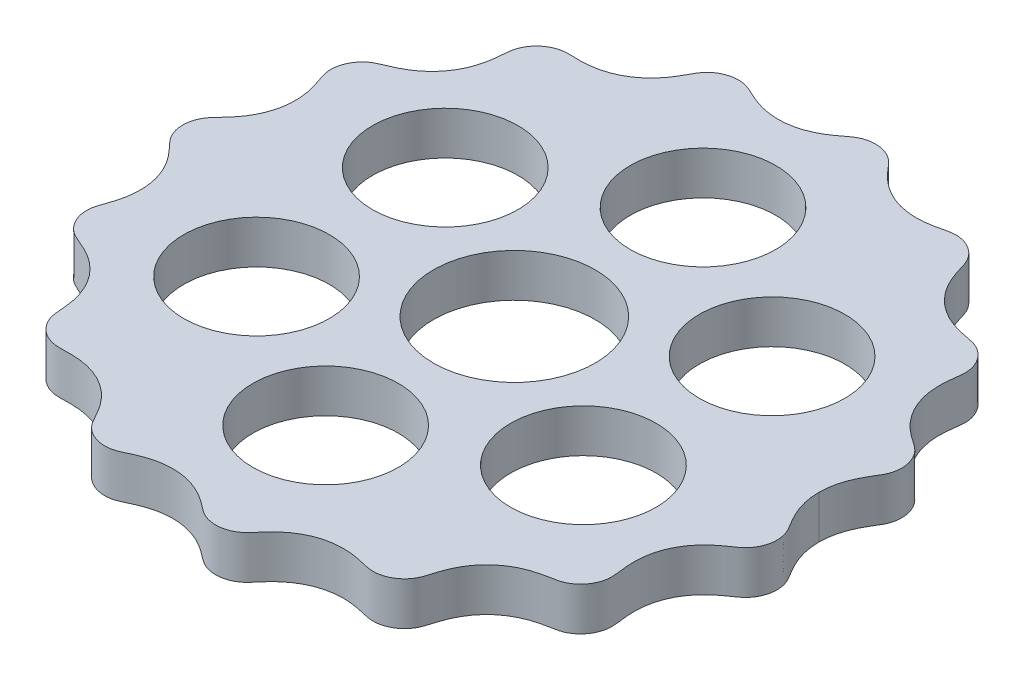
SolidWorks part; units mm, degrees
ref_plane "Front Plane" through (0, 0, 0) normal (0, 0, 1) x (1, 0, 0)
ref_plane "Top Plane" through (0, 0, 0) normal (0, 1, 0) x (1, 0, 0)
ref_plane "Right Plane" through (0, 0, 0) normal (1, 0, 0) x (0, 0, -1)
sketch "Sketch2" plane through (0, 0, 0) normal (0, 1, 0) x (1, 0, 0)
  circle A0 centre (0, 0) radius 35
  circle A1 centre (0, 35) radius 5.5
  circle A2 centre (13.3939, 32.3358) radius 5.5
  circle A3 centre (24.7487, 24.7487) radius 5.5
  circle A4 centre (32.3358, 13.3939) radius 5.5
  circle A5 centre (35, 0) radius 5.5
  circle A6 centre (32.3358, -13.3939) radius 5.5
  circle A7 centre (24.7487, -24.7487) radius 5.5
  circle A8 centre (13.3939, -32.3358) radius 5.5
  circle A9 centre (0, -35) radius 5.5
  circle A10 centre (-13.3939, -32.3358) radius 5.5
  circle A11 centre (-24.7487, -24.7487) radius 5.5
  circle A12 centre (-32.3358, -13.3939) radius 5.5
  circle A13 centre (-35, 0) radius 5.5
  circle A14 centre (-32.3358, 13.3939) radius 5.5
  circle A15 centre (-24.7487, 24.7487) radius 5.5
  circle A16 centre (-13.3939, 32.3358) radius 5.5
  point P14 (0, 0)
  dimension "D1" = 70
  dimension "D2" = 11
  dimension "D3" = 16
sketch "Sketch3" plane through (0, 0, 0) normal (0, 1, 0) x (1, 0, 0)
  line L0 (0, 0) -> (1.25, 0)
  circle A0 centre (1.25, 0) radius 17.5
  circle A1 centre (1.25, 0) radius 7.5
  circle A2 centre (1.25, 17.5) radius 6.75
  circle A3 centre (16.4054, 8.75) radius 6.75
  circle A4 centre (16.4054, -8.75) radius 6.75
  circle A5 centre (1.25, -17.5) radius 6.75
  circle A6 centre (-13.9054, -8.75) radius 6.75
  circle A7 centre (-13.9054, 8.75) radius 6.75
  spline S0 degree 4 poles (31.1366, 6.9847) (31.203, 6.8351) (31.3134, 6.5262) (31.4099, 6.0483) (31.4002, 5.404) (31.2697, 4.8647) (31.0757, 4.4461) (30.8859, 4.1207) (30.7324, 3.8696) (30.5414, 3.5556) (30.3222, 3.1725) (30.1219, 2.7738) (29.947, 2.3583) (29.8196, 1.9985) (29.7291, 1.6992) (29.6529, 1.3958) (29.5916, 1.0892) (29.551, 0.8187) (29.5259, 0.5847) (29.5113, 0.3932) (29.5036, 0.2322) (29.4998, 0.0635) (29.4996, -0.048) (29.5028, -0.2) (29.5088, -0.3457) (29.52, -0.516) (29.5395, -0.7199) (29.5727, -0.9729) (29.6257, -1.2689) (29.6959, -1.5759) (29.7851, -1.8912) (29.9157, -2.2793) (30.102, -2.7349) (30.335, -3.2008) (30.6126, -3.6776) (30.9341, -4.194) (31.2372, -4.7273) (31.4061, -5.3785) (31.4057, -6.1172) (31.2483, -6.8003) (30.9464, -7.4095) (30.5187, -7.9124) (30.0245, -8.2774) (29.5502, -8.595) (29.0554, -8.9568) (28.5566, -9.3788) (28.0713, -9.8763) (27.6188, -10.4563) (27.2335, -11.0884) (26.9232, -11.7651) (26.6937, -12.4782) (26.5492, -13.2173) (26.4929, -13.9285) (26.5065, -14.6008) (26.5673, -15.2309) (26.6512, -15.8162) (26.7167, -16.4473) (26.6264, -17.121) (26.3588, -17.7823) (25.9182, -18.3869) (25.3813, -18.8362) (24.7951, -19.1235) (24.2042, -19.2597) (23.6514, -19.3544) (23.1491, -19.4609) (22.7015, -19.5807) (22.2213, -19.7396) (21.7138, -19.9467) (21.1456, -20.242) (20.5337, -20.6545) (19.9693, -21.14) (19.4622, -21.6938) (19.0208, -22.3087) (18.6716, -22.937) (18.4029, -23.561) (18.1966, -24.1685) (18.0312, -24.7466) (17.8368, -25.3596) (17.4818, -25.9474) (16.963, -26.4532) (16.3026, -26.8344) (15.6052, -27.0309) (14.9186, -27.0444) (14.2906, -26.9063) (13.7073, -26.7605) (13.0779, -26.6354) (12.4032, -26.5561) (11.6845, -26.5443) (10.9313, -26.6191) (10.1981, -26.7814) (9.4956, -27.0274) (8.9144, -27.311) (8.4468, -27.5971) (8.0759, -27.8635) (7.7913, -28.0922) (7.4816, -28.3679) (7.1541, -28.6957) (6.8107, -29.0774) (6.4523, -29.5087) (6.0389, -29.9524) (5.497, -30.3164) (4.8394, -30.5567) (4.0956, -30.636) (3.389, -30.5371) (2.7605, -30.2784) (2.2467, -29.9061) (1.7817, -29.5409) (1.2664, -29.1732) (0.691, -28.8252) (0.0469, -28.5184) (-0.6654, -28.274) (-1.3977, -28.1162) (-2.139, -28.0466) (-2.879, -28.0642) (-3.6075, -28.1661) (-4.2811, -28.3376) (-4.8959, -28.5586) (-5.4566, -28.8062) (-5.9687, -29.0581) (-6.5321, -29.3036) (-7.1813, -29.4226) (-7.8826, -29.3781) (-8.5943, -29.1523) (-9.1983, -28.7803) (-9.6679, -28.2978) (-9.9878, -27.7564) (-10.2605, -27.2379) (-10.5768, -26.6962) (-10.9537, -26.1469) (-11.4088, -25.606) (-11.9502, -25.0925) (-12.5482, -24.6454) (-13.1945, -24.2723) (-13.8806, -23.9779) (-14.596, -23.7658) (-15.292, -23.6421) (-15.9562, -23.5904) (-16.5834, -23.5873) (-17.1688, -23.6104) (-17.7977, -23.6041) (-18.4504, -23.4386) (-19.0745, -23.1016) (-19.6258, -22.5981) (-20.0151, -22.013) (-20.2366, -21.3913) (-20.3057, -20.7807) (-20.3436, -20.2113) (-20.4095, -19.6018) (-20.5256, -18.9589) (-20.7138, -18.2898) (-20.9898, -17.608) (-21.3446, -16.9582) (-21.7755, -16.3511) (-22.2783, -15.7958) (-22.8461, -15.3011) (-23.4339, -14.8967) (-24.0229, -14.5724) (-24.599, -14.31) (-25.1478, -14.0899) (-25.7271, -13.8311) (-26.2654, -13.4161) (-26.7043, -12.8537) (-27.0076, -12.1698) (-27.1282, -11.4802) (-27.084, -10.8288) (-26.9064, -10.2491) (-26.7122, -9.7229) (-26.5247, -9.1481) (-26.3661, -8.5215) (-26.2605, -7.84) (-26.2278, -7.1092) (-26.2792, -6.3728) (-26.4175, -5.6414) (-26.6435, -4.9254) (-26.9163, -4.3218) (-27.1985, -3.8299) (-27.4942, -3.3917) (-27.7933, -3.0033) (-28.1536, -2.592) (-28.5722, -2.1595) (-28.9092, -1.79) (-29.1246, -1.4556) (-29.2527, -1.1931) (-29.3238, -1.0179) (-29.3829, -0.8388) (-29.4302, -0.6555) (-29.4612, -0.4933) (-29.4803, -0.3554) (-29.4914, -0.2338) (-29.4973, -0.1324) (-29.5007, -0.0226) (-29.5, 0.059) (-29.4956, 0.1702) (-29.4865, 0.2945) (-29.4732, 0.4119) (-29.4519, 0.545) (-29.4193, 0.6991) (-29.3684, 0.8884) (-29.2999, 1.0847) (-29.211, 1.2861) (-29.099, 1.4891) (-28.9873, 1.6605) (-28.8641, 1.8237) (-28.732, 1.9798) (-28.56, 2.1688) (-28.311, 2.4302) (-27.9922, 2.7711) (-27.6241, 3.2099) (-27.2613, 3.7219) (-26.8678, 4.4005) (-26.5022, 5.2703) (-26.3208, 6.0377) (-26.2588, 6.6626) (-26.2483, 6.9757) knots 0 0 0 0 0 0.005587 0.011173 0.016507 0.02184 0.02435 0.026861 0.029371 0.031882 0.036903 0.041924 0.044592 0.04726 0.049928 0.052596 0.055264 0.057932 0.059266 0.0606 0.061934 0.063268 0.064442 0.065615 0.066789 0.067963 0.070311 0.072658 0.075454 0.07825 0.081046 0.083842 0.089434 0.095025 0.098832 0.102639 0.110253 0.115841 0.12143 0.127693 0.133956 0.138834 0.143712 0.148591 0.153469 0.159735 0.166 0.172266 0.178532 0.184946 0.191361 0.197775 0.20419 0.209244 0.214299 0.219354 0.224409 0.23082 0.23723 0.243461 0.249691 0.254486 0.25928 0.264075 0.26887 0.271986 0.275101 0.281333 0.287565 0.293796 0.300242 0.306689 0.313135 0.319581 0.324722 0.329863 0.335004 0.340145 0.346588 0.353031 0.359474 0.365917 0.371058 0.376199 0.38134 0.386481 0.392928 0.399374 0.40582 0.412266 0.418498 0.424729 0.427845 0.430961 0.434077 0.437193 0.441987 0.446782 0.451577 0.456371 0.462602 0.468832 0.475243 0.481654 0.486709 0.491763 0.496818 0.501873 0.508287 0.514702 0.521116 0.527531 0.533796 0.540062 0.546328 0.552593 0.557472 0.56235 0.567228 0.572107 0.57837 0.584633 0.590985 0.597337 0.602346 0.607354 0.612363 0.617371 0.623727 0.630083 0.636439 0.642795 0.649151 0.655506 0.661862 0.668218 0.673227 0.678235 0.683244 0.688252 0.694604 0.700957 0.70722 0.713483 0.718361 0.723239 0.728118 0.732996 0.739262 0.745527 0.751793 0.758059 0.764473 0.770888 0.777302 0.783717 0.788771 0.793826 0.798881 0.803936 0.810347 0.816757 0.822988 0.829218 0.834013 0.838807 0.843602 0.848397 0.854628 0.86086 0.867092 0.873323 0.879769 0.886216 0.892662 0.895885 0.899108 0.904249 0.90939 0.914531 0.919672 0.921283 0.922894 0.924505 0.926115 0.927726 0.929337 0.930142 0.930947 0.931753 0.932558 0.933896 0.934564 0.935233 0.93657 0.937908 0.939245 0.940582 0.943257 0.945002 0.946746 0.948491 0.950235 0.95198 0.953724 0.957213 0.962562 0.967911 0.973259 0.978608 0.989304 1 1 1 1 1 construction
  spline S1 degree 4 poles (29.5, 0) (29.5, -0.0299) (29.5005, -0.0898) (29.5028, -0.2) (29.5088, -0.3457) (29.52, -0.516) (29.5395, -0.7199) (29.5727, -0.9729) (29.6257, -1.2689) (29.6959, -1.5759) (29.7851, -1.8912) (29.9157, -2.2793) (30.102, -2.7349) (30.335, -3.2008) (30.6126, -3.6776) (30.9341, -4.194) (31.2372, -4.7273) (31.4061, -5.3785) (31.4057, -6.1172) (31.2483, -6.8003) (30.9464, -7.4095) (30.5187, -7.9124) (30.0245, -8.2774) (29.5502, -8.595) (29.0554, -8.9568) (28.5566, -9.3788) (28.0713, -9.8763) (27.6188, -10.4563) (27.2335, -11.0884) (26.9232, -11.7651) (26.6937, -12.4782) (26.5492, -13.2173) (26.4929, -13.9285) (26.5065, -14.6008) (26.5673, -15.2309) (26.6512, -15.8162) (26.7167, -16.4473) (26.6264, -17.121) (26.3588, -17.7823) (25.9182, -18.3869) (25.3813, -18.8362) (24.7951, -19.1235) (24.2042, -19.2597) (23.6514, -19.3544) (23.1491, -19.4609) (22.7015, -19.5807) (22.2213, -19.7396) (21.7138, -19.9467) (21.1456, -20.242) (20.5337, -20.6545) (19.9693, -21.14) (19.4622, -21.6938) (19.0208, -22.3087) (18.6716, -22.937) (18.4029, -23.561) (18.1966, -24.1685) (18.0312, -24.7466) (17.8368, -25.3596) (17.4818, -25.9474) (16.963, -26.4532) (16.3026, -26.8344) (15.6052, -27.0309) (14.9186, -27.0444) (14.2906, -26.9063) (13.7073, -26.7605) (13.0779, -26.6354) (12.4032, -26.5561) (11.6845, -26.5443) (10.9313, -26.6191) (10.1981, -26.7814) (9.4956, -27.0274) (8.9144, -27.311) (8.4468, -27.5971) (8.0759, -27.8635) (7.7913, -28.0922) (7.4816, -28.3679) (7.1541, -28.6957) (6.8107, -29.0774) (6.4523, -29.5087) (6.0389, -29.9524) (5.497, -30.3164) (4.8394, -30.5567) (4.0956, -30.636) (3.389, -30.5371) (2.7605, -30.2784) (2.2467, -29.9061) (1.7817, -29.5409) (1.2664, -29.1732) (0.691, -28.8252) (0.0469, -28.5184) (-0.6654, -28.274) (-1.3977, -28.1162) (-2.139, -28.0466) (-2.879, -28.0642) (-3.6075, -28.1661) (-4.2811, -28.3376) (-4.8959, -28.5586) (-5.4566, -28.8062) (-5.9687, -29.0581) (-6.5321, -29.3036) (-7.1813, -29.4226) (-7.8826, -29.3781) (-8.5943, -29.1523) (-9.1983, -28.7803) (-9.6679, -28.2978) (-9.9878, -27.7564) (-10.2605, -27.2379) (-10.5768, -26.6962) (-10.9537, -26.1469) (-11.4088, -25.606) (-11.9502, -25.0925) (-12.5482, -24.6454) (-13.1945, -24.2723) (-13.8806, -23.9779) (-14.596, -23.7658) (-15.292, -23.6421) (-15.9562, -23.5904) (-16.5834, -23.5873) (-17.1688, -23.6104) (-17.7977, -23.6041) (-18.4504, -23.4386) (-19.0745, -23.1016) (-19.6258, -22.5981) (-20.0151, -22.013) (-20.2366, -21.3913) (-20.3057, -20.7807) (-20.3436, -20.2113) (-20.4095, -19.6018) (-20.5256, -18.9589) (-20.7138, -18.2898) (-20.9898, -17.608) (-21.3446, -16.9582) (-21.7755, -16.3511) (-22.2783, -15.7958) (-22.8461, -15.3011) (-23.4339, -14.8967) (-24.0229, -14.5724) (-24.599, -14.31) (-25.1478, -14.0899) (-25.7271, -13.8311) (-26.2654, -13.4161) (-26.7043, -12.8537) (-27.0076, -12.1698) (-27.1282, -11.4802) (-27.084, -10.8288) (-26.9064, -10.2491) (-26.7122, -9.7229) (-26.5247, -9.1481) (-26.3661, -8.5215) (-26.2605, -7.84) (-26.2278, -7.1092) (-26.2792, -6.3728) (-26.4175, -5.6414) (-26.6435, -4.9254) (-26.9163, -4.3218) (-27.1985, -3.8299) (-27.4942, -3.3917) (-27.7933, -3.0033) (-28.1536, -2.592) (-28.5722, -2.1595) (-28.9092, -1.79) (-29.1246, -1.4556) (-29.2527, -1.1931) (-29.3238, -1.0179) (-29.3829, -0.8388) (-29.4302, -0.6555) (-29.4612, -0.4933) (-29.4803, -0.3554) (-29.4914, -0.2338) (-29.4973, -0.1324) (-29.4995, -0.0617) (-29.5, -0.0205) (-29.5, 0) knots 0.063268 0.063268 0.063268 0.063268 0.063268 0.064442 0.065615 0.066789 0.067963 0.070311 0.072658 0.075454 0.07825 0.081046 0.083842 0.089434 0.095025 0.098832 0.102639 0.110253 0.115841 0.12143 0.127693 0.133956 0.138834 0.143712 0.148591 0.153469 0.159735 0.166 0.172266 0.178532 0.184946 0.191361 0.197775 0.20419 0.209244 0.214299 0.219354 0.224409 0.23082 0.23723 0.243461 0.249691 0.254486 0.25928 0.264075 0.26887 0.271986 0.275101 0.281333 0.287565 0.293796 0.300242 0.306689 0.313135 0.319581 0.324722 0.329863 0.335004 0.340145 0.346588 0.353031 0.359474 0.365917 0.371058 0.376199 0.38134 0.386481 0.392928 0.399374 0.40582 0.412266 0.418498 0.424729 0.427845 0.430961 0.434077 0.437193 0.441987 0.446782 0.451577 0.456371 0.462602 0.468832 0.475243 0.481654 0.486709 0.491763 0.496818 0.501873 0.508287 0.514702 0.521116 0.527531 0.533796 0.540062 0.546328 0.552593 0.557472 0.56235 0.567228 0.572107 0.57837 0.584633 0.590985 0.597337 0.602346 0.607354 0.612363 0.617371 0.623727 0.630083 0.636439 0.642795 0.649151 0.655506 0.661862 0.668218 0.673227 0.678235 0.683244 0.688252 0.694604 0.700957 0.70722 0.713483 0.718361 0.723239 0.728118 0.732996 0.739262 0.745527 0.751793 0.758059 0.764473 0.770888 0.777302 0.783717 0.788771 0.793826 0.798881 0.803936 0.810347 0.816757 0.822988 0.829218 0.834013 0.838807 0.843602 0.848397 0.854628 0.86086 0.867092 0.873323 0.879769 0.886216 0.892662 0.895885 0.899108 0.904249 0.90939 0.914531 0.919672 0.921283 0.922894 0.924505 0.926115 0.927726 0.929337 0.930142 0.930947 0.931753 0.932558 0.932558 0.932558 0.932558 0.932558
  spline S2 degree 4 poles (29.5, 0) (29.5, 0.0299) (29.5005, 0.0898) (29.5028, 0.2) (29.5088, 0.3457) (29.52, 0.516) (29.5395, 0.7199) (29.5727, 0.9729) (29.6257, 1.2689) (29.6959, 1.5759) (29.7851, 1.8912) (29.9157, 2.2793) (30.102, 2.7349) (30.335, 3.2008) (30.6126, 3.6776) (30.9341, 4.194) (31.2372, 4.7273) (31.4061, 5.3785) (31.4057, 6.1172) (31.2483, 6.8003) (30.9464, 7.4095) (30.5187, 7.9124) (30.0245, 8.2774) (29.5502, 8.595) (29.0554, 8.9568) (28.5566, 9.3788) (28.0713, 9.8763) (27.6188, 10.4563) (27.2335, 11.0884) (26.9232, 11.7651) (26.6937, 12.4782) (26.5492, 13.2173) (26.4929, 13.9285) (26.5065, 14.6008) (26.5673, 15.2309) (26.6512, 15.8162) (26.7167, 16.4473) (26.6264, 17.121) (26.3588, 17.7823) (25.9182, 18.3869) (25.3813, 18.8362) (24.7951, 19.1235) (24.2042, 19.2597) (23.6514, 19.3544) (23.1491, 19.4609) (22.7015, 19.5807) (22.2213, 19.7396) (21.7138, 19.9467) (21.1456, 20.242) (20.5337, 20.6545) (19.9693, 21.14) (19.4622, 21.6938) (19.0208, 22.3087) (18.6716, 22.937) (18.4029, 23.561) (18.1966, 24.1685) (18.0312, 24.7466) (17.8368, 25.3596) (17.4818, 25.9474) (16.963, 26.4532) (16.3026, 26.8344) (15.6052, 27.0309) (14.9186, 27.0444) (14.2906, 26.9063) (13.7073, 26.7605) (13.0779, 26.6354) (12.4032, 26.5561) (11.6845, 26.5443) (10.9313, 26.6191) (10.1981, 26.7814) (9.4956, 27.0274) (8.9144, 27.311) (8.4468, 27.5971) (8.0759, 27.8635) (7.7913, 28.0922) (7.4816, 28.3679) (7.1541, 28.6957) (6.8107, 29.0774) (6.4523, 29.5087) (6.0389, 29.9524) (5.497, 30.3164) (4.8394, 30.5567) (4.0956, 30.636) (3.389, 30.5371) (2.7605, 30.2784) (2.2467, 29.9061) (1.7817, 29.5409) (1.2664, 29.1732) (0.691, 28.8252) (0.0469, 28.5184) (-0.6654, 28.274) (-1.3977, 28.1162) (-2.139, 28.0466) (-2.879, 28.0642) (-3.6075, 28.1661) (-4.2811, 28.3376) (-4.8959, 28.5586) (-5.4566, 28.8062) (-5.9687, 29.0581) (-6.5321, 29.3036) (-7.1813, 29.4226) (-7.8826, 29.3781) (-8.5943, 29.1523) (-9.1983, 28.7803) (-9.6679, 28.2978) (-9.9878, 27.7564) (-10.2605, 27.2379) (-10.5768, 26.6962) (-10.9537, 26.1469) (-11.4088, 25.606) (-11.9502, 25.0925) (-12.5482, 24.6454) (-13.1945, 24.2723) (-13.8806, 23.9779) (-14.596, 23.7658) (-15.292, 23.6421) (-15.9562, 23.5904) (-16.5834, 23.5873) (-17.1688, 23.6104) (-17.7977, 23.6041) (-18.4504, 23.4386) (-19.0745, 23.1016) (-19.6258, 22.5981) (-20.0151, 22.013) (-20.2366, 21.3913) (-20.3057, 20.7807) (-20.3436, 20.2113) (-20.4095, 19.6018) (-20.5256, 18.9589) (-20.7138, 18.2898) (-20.9898, 17.608) (-21.3446, 16.9582) (-21.7755, 16.3511) (-22.2783, 15.7958) (-22.8461, 15.3011) (-23.4339, 14.8967) (-24.0229, 14.5724) (-24.599, 14.31) (-25.1478, 14.0899) (-25.7271, 13.8311) (-26.2654, 13.4161) (-26.7043, 12.8537) (-27.0076, 12.1698) (-27.1282, 11.4802) (-27.084, 10.8288) (-26.9064, 10.2491) (-26.7122, 9.7229) (-26.5247, 9.1481) (-26.3661, 8.5215) (-26.2605, 7.84) (-26.2278, 7.1092) (-26.2792, 6.3728) (-26.4175, 5.6414) (-26.6435, 4.9254) (-26.9163, 4.3218) (-27.1985, 3.8299) (-27.4942, 3.3917) (-27.7933, 3.0033) (-28.1536, 2.592) (-28.5722, 2.1595) (-28.9092, 1.79) (-29.1246, 1.4556) (-29.2527, 1.1931) (-29.3238, 1.0179) (-29.3829, 0.8388) (-29.4302, 0.6555) (-29.4612, 0.4933) (-29.4803, 0.3554) (-29.4914, 0.2338) (-29.4973, 0.1324) (-29.4995, 0.0617) (-29.5, 0.0205) (-29.5, 0) knots 0.063268 0.063268 0.063268 0.063268 0.063268 0.064442 0.065615 0.066789 0.067963 0.070311 0.072658 0.075454 0.07825 0.081046 0.083842 0.089434 0.095025 0.098832 0.102639 0.110253 0.115841 0.12143 0.127693 0.133956 0.138834 0.143712 0.148591 0.153469 0.159735 0.166 0.172266 0.178532 0.184946 0.191361 0.197775 0.20419 0.209244 0.214299 0.219354 0.224409 0.23082 0.23723 0.243461 0.249691 0.254486 0.25928 0.264075 0.26887 0.271986 0.275101 0.281333 0.287565 0.293796 0.300242 0.306689 0.313135 0.319581 0.324722 0.329863 0.335004 0.340145 0.346588 0.353031 0.359474 0.365917 0.371058 0.376199 0.38134 0.386481 0.392928 0.399374 0.40582 0.412266 0.418498 0.424729 0.427845 0.430961 0.434077 0.437193 0.441987 0.446782 0.451577 0.456371 0.462602 0.468832 0.475243 0.481654 0.486709 0.491763 0.496818 0.501873 0.508287 0.514702 0.521116 0.527531 0.533796 0.540062 0.546328 0.552593 0.557472 0.56235 0.567228 0.572107 0.57837 0.584633 0.590985 0.597337 0.602346 0.607354 0.612363 0.617371 0.623727 0.630083 0.636439 0.642795 0.649151 0.655506 0.661862 0.668218 0.673227 0.678235 0.683244 0.688252 0.694604 0.700957 0.70722 0.713483 0.718361 0.723239 0.728118 0.732996 0.739262 0.745527 0.751793 0.758059 0.764473 0.770888 0.777302 0.783717 0.788771 0.793826 0.798881 0.803936 0.810347 0.816757 0.822988 0.829218 0.834013 0.838807 0.843602 0.848397 0.854628 0.86086 0.867092 0.873323 0.879769 0.886216 0.892662 0.895885 0.899108 0.904249 0.90939 0.914531 0.919672 0.921283 0.922894 0.924505 0.926115 0.927726 0.929337 0.930142 0.930947 0.931753 0.932558 0.932558 0.932558 0.932558 0.932558
  point P20 (1.25, 0)
  dimension "D2" = 35
  dimension "D3" = 13.5
  dimension "D4" = 15
  dimension "D1" = 1.25
  dimension "D5" = 6
extrude "Boss-Extrude1" add sketch "Sketch3" along normal blind 4 contours S1 S2 A7 A0 A2 A3 A4 A5 A6 | A7 A0 A6 A5 A4 A3 A2 A1 region at (18.2341, 0, 1.152) region at (1.9228, 0, 28.5863)
sketch "Sketch4" plane through (0, 0, 0) normal (0, -1, 0) x (-1, 0, 0)
  circle A0 centre (0, 0) radius 17.5
  circle A1 centre (0, 17.5) radius 5.5
  circle A2 centre (15.1554, 8.75) radius 5.5
  circle A3 centre (15.1554, -8.75) radius 5.5
  circle A4 centre (0, -17.5) radius 5.5
  circle A5 centre (-15.1554, -8.75) radius 5.5
  circle A6 centre (-15.1554, 8.75) radius 5.5
  point P16 (0, 0)
  dimension "D2" = 11
  dimension "D1" = 35
  dimension "D3" = 6
equation "\"R_SUN\"=35"
equation "\"D1@Sketch2\"=2*\"R_SUN\""
equation "\"R_ROLL\"=5.5"
equation "\"D2@Sketch2\"=2*\"R_ROLL\""
equation "\"GRATIO\"=15"
equation "\"D3@Sketch2\"=\"GRATIO\"+1"
equation "\"RHO\"=1.25"
equation "\"D1@Sketch3\"=\"RHO\""
equation "\"D_PIN_SPACE\"=35"
equation "\"D_PIN\"=11"
equation "\"D3@Sketch3\"=\"D_PIN\"+2*\"RHO\""
equation "\"D_IN\"=15"
equation "\"D4@Sketch3\"=\"D_IN\""
equation "\"NUM_PINS\"=6"
equation "\"D5@Sketch3\"=\"NUM_PINS\""
equation "\"THICK\"=4"
equation "\"D1@Boss-Extrude1\"=\"THICK\""
equation "\"D_BOLTS\"=35"
equation "\"D1@Sketch4\"=\"D_BOLTS\""
equation "\"R_BEAR\"=11"
equation "\"D2@Sketch4\"=\"R_BEAR\""
equation "\"NUM_BOLT\"=6"
equation "\"D3@Sketch4\"=\"NUM_BOLT\""
